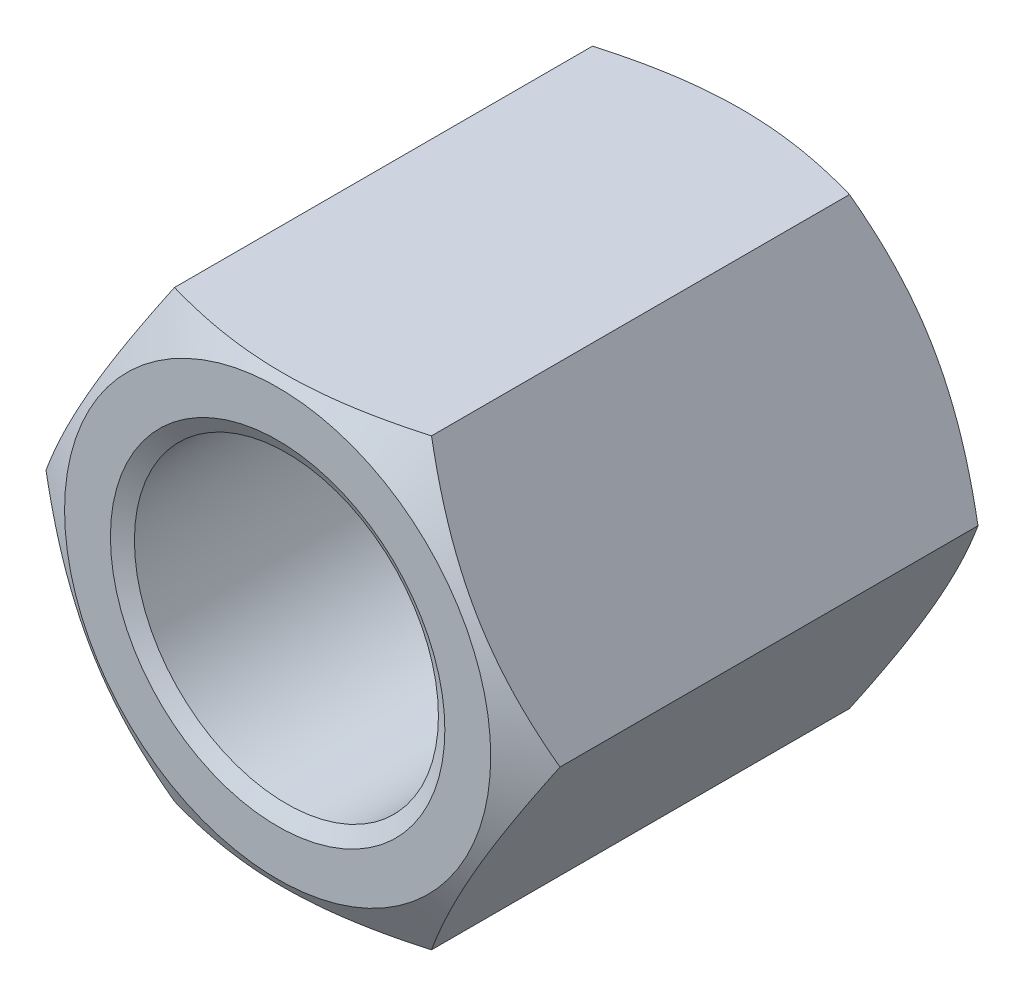
SolidWorks part; units mm, degrees
ref_plane "Front" through (0, 0, 0) normal (0, 0, 1) x (1, 0, 0)
ref_plane "Top" through (0, 0, 0) normal (0, 1, 0) x (1, 0, 0)
ref_plane "Right" through (0, 0, 0) normal (1, 0, 0) x (0, 0, -1)
sketch "Sketch1" plane through (0, 0, 0) normal (0, 0, 1) x (1, 0, 0)
  line L1 (5.072, -8.785) -> (10.144, 0)
  line L2 (10.144, 0) -> (5.072, 8.785)
  line L3 (5.072, 8.785) -> (-5.072, 8.785)
  line L4 (-5.072, 8.785) -> (-10.144, 0)
  line L5 (-10.144, 0) -> (-5.072, -8.785)
  line L6 (-5.072, -8.785) -> (5.072, -8.785)
  circle A0 centre (0, 0) radius 8.785 construction
  circle A1 centre (0, 0) radius 6
extrude "BaseNut" add sketch "Sketch1" against normal blind 18.5
cosmetic thread "ThreadCosmetic1" [suppressed] parameters "D2"=13
sketch "Sketch2" plane through (0, 0, 0) normal (0, 1, 0) x (1, 0, 0)
  line L0 (-10.144, 18.5) -> (-8.41, 18.5)
  line L2 (-8.41, 18.5) -> (-10.144, 17.4988)
  line L3 (-10.144, 17.4988) -> (-10.144, 18.5)
  line L4 (0, 3.3759) -> (0, -9.8171) construction
  line L6 (-9.7712, 9.25) -> (9.8853, 9.25) construction
  line L7 (-10.144, 1.0012) -> (-10.144, 0)
  line L8 (-8.41, 0) -> (-10.144, 1.0012)
  line L9 (-10.144, 0) -> (-8.41, 0)
  dimension "D1" = 30
  dimension "D2" = 9.25
revolve "Double-Chamfer" cut sketch "Sketch2" angle 360 about L4
chamfer "EndChamfer" distance 0.6 angle 30 2 edges at (6, 0, 0) (6, 0, -18.5) first distance on face at (-8.41, 0, 0) first distance on face at (6, 0, -18.5)
sketch "Sketch3" plane through (0, 0, 0) normal (0, 1, 0) x (1, 0, 0)
  line L0 (0, 28.565) -> (0, -12.1255) construction
  line L1 (5.5, 18.15) -> (6, 18.15)
  line L2 (6, 18.15) -> (6.433, 17.9)
  line L3 (6.433, 17.9) -> (6, 17.65)
  line L4 (6, 17.65) -> (5.5, 17.65)
  line L5 (5.5, 17.65) -> (5.5, 18.15)
  line L6 (6, 17.9) -> (-6, 17.9) construction
  dimension "D1" = 0.5
  dimension "D2" = 12
revolve "Cut-Revolve10" [suppressed] cut sketch "Sketch3" angle 360 about L0
pattern_linear "LPattern10" [suppressed] count 30 spacing 0.6 along (0, 0, 1) of bodies 103
equation "\"dw@Sketch2\" = \"s@Sketch1\" - 0.75"
equation "\"D2@Sketch2\" = \"m@BaseNut\" / 2"
equation "\"D1@EndChamfer\" = \"D@Sketch1\" / 20"
equation "\"D1@Sketch3\" = (  \"D2@ThreadCosmetic1\" - \"D@Sketch1\" )  / 2"
equation "\"D2@Sketch3\" = \"D@Sketch1\""
equation "\"D3@LPattern10\" = \"D1@Sketch3\" * 1.2"
equation "\"D1@LPattern10\" = (  \"m@BaseNut\"  - \"D1@EndChamfer\")  / \"D3@LPattern10\" "
